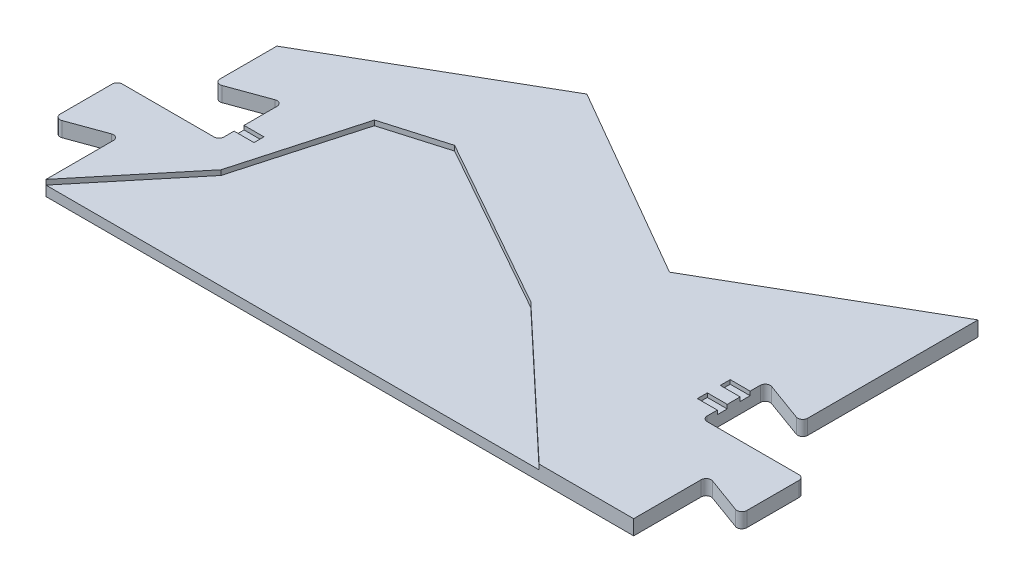
SolidWorks part; units mm, degrees
ref_plane "Přední rovina" through (0, 0, 0) normal (0, 0, 1) x (1, 0, 0)
ref_plane "Horní rovina" through (0, 0, 0) normal (0, 1, 0) x (1, 0, 0)
ref_plane "Pravá rovina" through (0, 0, 0) normal (1, 0, 0) x (0, 0, -1)
sketch "Skica1" plane through (0, 0, 0) normal (0, 1, 0) x (1, 0, 0)
  line L0 (-118.1438, 0) -> (-118.1438, 15)
  line L1 (-118.1438, 15) -> (-128.0938, 11.3785)
  line L2 (-128.0938, 11.3785) -> (-128.0938, 24.2785)
  line L3 (-107.6438, 24.2785) -> (-107.6438, 37.3785)
  line L4 (-107.6438, 37.3785) -> (-118.1432, 33.557)
  line L5 (-118.1432, 33.557) -> (-118.1432, 46.4149)
  line L6 (-118.1432, 46.4149) -> (-78.6351, 69.2249)
  line L7 (-78.6351, 69.2249) -> (-39.3176, 46.5249)
  line L8 (-118.1438, 15) -> (-118.1438, 58.9257) construction
  line L9 (-107.6438, 24.2785) -> (-128.0938, 24.2785)
  line L10 (-118.1438, 0) -> (-102.2271, 19.2785)
  line L11 (-102.2271, 19.2785) -> (-95.473, 43.3489)
  line L12 (-95.473, 43.3489) -> (-82.9972, 47.0032)
  line L13 (-82.9972, 47.0032) -> (-48.113, 27.4305)
  line L14 (-39.3176, 46.5249) -> (0, 69.2249)
  line L15 (-118.1438, 0) -> (0, 0)
  line L16 (-48.113, 27.4305) -> (-19, 0)
  line L17 (0, 0) -> (0, 15)
  line L18 (0, 69.2249) -> (0, 0) construction
  line L19 (-10.5, 24.2783) -> (9.9505, 24.2783)
  line L20 (0, 69.2249) -> (0, 33.5566)
  line L21 (0, 15) -> (9.9505, 11.3783)
  line L22 (9.9505, 24.2783) -> (9.9505, 11.3783)
  line L23 (0, 33.5566) -> (-10.5, 37.3783)
  line L24 (-10.5, 37.3783) -> (-10.5, 24.2783)
  point P23 (-0.2747, 24.2783)
  dimension "D1" = 45.4
  dimension "D2" = 45.62
  dimension "D3" = 120
  dimension "D4" = 70
  dimension "D5" = 12.9
  dimension "D6" = 13.1
  dimension "D7" = 15
  dimension "D8" = 69.2249
  dimension "D9" = 69.2249
  dimension "D10" = 25
  dimension "D11" = 25
  dimension "D12" = 13
  dimension "D13" = 40
  dimension "D14" = 45.4
  dimension "D15" = 120
  dimension "D16" = 118.1438
  dimension "D17" = 40
  dimension "D18" = 122
  dimension "D19" = 15
  dimension "D20" = 70
  dimension "D21" = 70
  dimension "D22" = 5
  dimension "D23" = 120
  dimension "D24" = 19
  dimension "D25" = 166
  dimension "D26" = 10.5
  dimension "D27" = 12.9
  dimension "D28" = 13.1
  dimension "D29" = 10.5
  dimension "D30" = 70
  dimension "D31" = 9.95
extrude "Přidat vysunutím1" add sketch "Skica1" along normal blind 3 contours L24 L23 L20 L14 L7 L6 L5 L4 L3 L9 L2 L1 L0 L10 L11 L12 L13 L16 L15 L17 L21 L22 L19 region at (-50.0339, 0, -36.1877)
extrude "Přidat vysunutím2" add sketch "Skica1<3>" along normal blind 2 contours L16 L13 L12 L11 L10 L15 region at (-72.3465, 0, -17.3507)
sketch "Skica1<3>" plane through (0, 0, 0) normal (0, 1, 0) x (1, 0, 0) same geometry as "Skica1"
fillet "Zaoblit3" radius 1 12 edges at (-107.6438, 1.5, -24.2785) (0, 1.5, -15) (9.9505, 1.5, -11.3783) (9.9505, 1.5, -24.2783) (-10.5, 1.5, -24.2783) (-10.5, 1.5, -37.3783) (0, 1.5, -33.5566) (-118.1438, 1.5, -15) (-128.0938, 1.5, -11.3785) (-128.0938, 1.5, -24.2785) (-107.6438, 1.5, -37.3785) (-118.1432, 1.5, -33.557)
sketch "Skica2" plane through (0, 3, 0) normal (0, 1, 0) x (1, 0, 0)
  line L0 (-107.6438, 30.6144) -> (-99.0463, 30.6144) construction
  line L1 (-107.6438, 25.2785) -> (-107.6438, 35.9503) construction
  line L7 (-102.2271, 19.2785) -> (-95.473, 43.3489) construction
  line L10 (-107.6438, 29.3144) -> (-103.6438, 29.3144)
  line L11 (-103.6438, 29.3144) -> (-103.6438, 27.3144)
  line L12 (-103.6438, 27.3144) -> (-107.6438, 27.3144)
  line L13 (-107.6438, 29.3144) -> (-107.6438, 27.3144)
  dimension "D1" = 1.3
  dimension "D2" = 2
  dimension "D3" = 4
extrude "Odebrat vysunutím1" cut sketch "Skica2" against normal blind 0.8
sketch "Skica3" plane through (0, 3, 0) normal (0, 1, 0) x (1, 0, 0)
  line L0 (-10.5, 30.6142) -> (-49.1857, 30.6142) construction
  line L1 (-10.5, 33.9142) -> (-14.5, 33.9142)
  line L2 (-14.5, 33.9142) -> (-14.5, 31.9142)
  line L3 (-14.5, 31.9142) -> (-10.5, 31.9142)
  line L4 (-14.5, 27.3142) -> (-14.5, 29.3142)
  line L5 (-14.5, 29.3142) -> (-10.5, 29.3142)
  line L6 (-10.5, 27.3142) -> (-14.5, 27.3142)
  line L7 (-10.5, 33.9142) -> (-10.5, 31.9142)
  line L8 (-10.5, 29.3142) -> (-10.5, 27.3142)
  line L9 (-10.5, 35.9502) -> (-10.5, 25.2783) construction
  point P10 (-10.5, 30.6142)
  point P11 (0, 0)
  point P14 (0, 0)
  dimension "D1" = 2
  dimension "D2" = 4
  dimension "D3" = 2.6
extrude "Odebrat vysunutím2" cut sketch "Skica3" against normal blind 0.8
